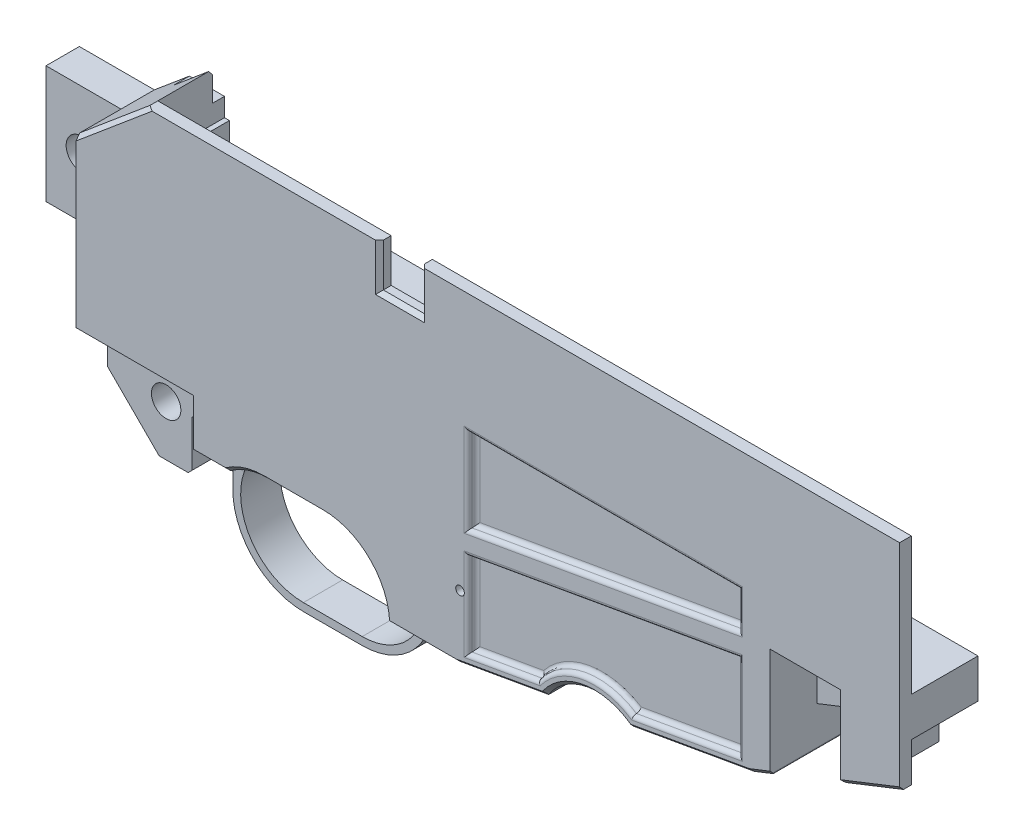
SolidWorks part; units mm, degrees
ref_plane "정면" through (0, 0, 0) normal (0, 0, 1) x (1, 0, 0)
ref_plane "윗면" through (0, 0, 0) normal (0, 1, 0) x (1, 0, 0)
ref_plane "우측면" through (0, 0, 0) normal (1, 0, 0) x (0, 0, -1)
sketch "스케치2" plane through (0, 0, 0) normal (0, 0, 1) x (1, 0, 0)
  line L0 (0, 0) -> (20, 0)
  line L1 (20, 0) -> (37.8763, 15)
  line L2 (37.8763, 15) -> (230, 15)
  line L3 (230, 15) -> (230, -54.9955)
  line L4 (230, -54.9955) -> (192, -54.9955)
  line L5 (117, -68.22) -> (101, -68.22)
  line L6 (0, 0) -> (0, -30)
  line L7 (0, -30) -> (20, -30)
  line L8 (20, -30) -> (20, -55)
  line L9 (20, -55) -> (33.22, -68.22)
  line L10 (33.22, -68.22) -> (50, -68.22)
  line L11 (117, -68.22) -> (139.5521, -64.2435)
  line L12 (68, -68.22) -> (83, -68.22) construction
  line L13 (68, -52.22) -> (83, -52.22)
  line L14 (68, -84.22) -> (83, -84.22)
  line L15 (161.2179, -60.4232) -> (192, -54.9955)
  line L16 (68, -86.22) -> (83, -86.22)
  line L17 (71.3269, -49.22) -> (86.3269, -49.22)
  line L19 (68, -50.22) -> (83, -50.22) construction
  arc A0 (68, -52.22) -> (68, -84.22) centre (68, -68.22) ccw
  arc A1 (83, -84.22) -> (83, -52.22) centre (83, -68.22) ccw
  arc A2 (83, -86.22) -> (101, -68.22) centre (83, -68.22) ccw
  arc A3 (50, -68.22) -> (68, -86.22) centre (68, -68.22) ccw
  arc A5 (139.5521, -64.2435) -> (161.2179, -60.4232) centre (152.1559, -72.3764) cw
  arc A6 (68, -50.22) -> (68, -86.22) centre (68, -68.22) ccw construction
  arc A7 (83, -86.22) -> (83, -50.22) centre (83, -68.22) ccw construction
  point P16 (75.5, -68.22)
  point P27 (50, -68.22)
  point P30 (101, -68.22)
  point P34 (139.5521, -64.2435)
  point P35 (161.2179, -60.4232)
  dimension "D11" = 16
  dimension "D15" = 22
  dimension "D16" = 15
  dimension "D1" = 230
  dimension "D2" = 30
  dimension "D3" = 30
  dimension "D4" = 135
  dimension "D5" = 140
  dimension "D6" = 15
  dimension "D7" = 75
  dimension "D8" = 16
  dimension "D9" = 15
  dimension "D12" = 3
  dimension "D13" = 64.22
  dimension "D14" = 170
  dimension "D17" = 20
  dimension "D18" = 25
  dimension "D19" = 16
  dimension "D20" = 22.9
  dimension "D21" = 20
  dimension "D10" = 2
extrude "보스-돌출1" add sketch "스케치2" along normal blind 20 contours A5 L15 L4 L3 L2 L1 L0 L6 L7 L8 L9 L10 A3 L16 A2 L5 A1 L14 A0 L13 region at (119.6066, -23.0148, 0)
sketch "스케치3" plane through (0, 0, 0) normal (0, 0, -1) x (-1, 0, 0)
  line L0 (-68, -52.22) -> (-83, -52.22) construction
  line L1 (-39.125, -49.22) -> (-111.875, -49.22)
  line L2 (-39.125, -49.22) -> (-39.125, 2.78)
  line L3 (-39.125, 2.78) -> (-111.875, 2.78)
  line L4 (-111.875, -49.22) -> (-111.875, 2.78)
  line L5 (-75.5, -52.22) -> (-75.5, -49.22) construction
  point P6 (-75.5, -52.22)
  point P9 (-75.5, -49.22)
  dimension "D1" = 52
  dimension "D2" = 72.75
  dimension "D3" = 3
extrude "컷-돌출1" cut sketch "스케치3" against normal blind 8.25
sketch "스케치4" plane through (0, 0, 0) normal (0, 0, -1) x (-1, 0, 0)
  line L1 (-37.8763, 2.78) -> (-211, 2.78)
  line L3 (-37.8763, 15) -> (-211, 15)
  line L4 (-211, 2.78) -> (-211, 15)
  line L5 (-37.8763, 2.78) -> (-37.8763, 15)
  line L6 (-211, -54.9955) -> (-211, 15) construction
  line L7 (-230, -54.9955) -> (-192, -54.9955) construction
  line L8 (-37.8763, 15) -> (-230, 15) construction
  dimension "D2" = 12.22
extrude "컷-돌출2" cut sketch "스케치4" against normal blind 17
sketch "스케치5" plane through (0, 0, 0) normal (0, 0, -1) x (-1, 0, 0)
  line L0 (-117, -68.22) -> (-117, 2.78)
  line L1 (-117, 2.78) -> (-192, 2.78)
  line L2 (-192, 2.78) -> (-192, -54.9955)
  line L3 (-211, 2.78) -> (-37.8763, 2.78) construction
  line L5 (-192, -54.9955) -> (-161.2179, -60.4232)
  line L6 (-139.5521, -64.2435) -> (-117, -68.22)
  line L7 (-117, -68.22) -> (-120.7282, -69.1071)
  arc A0 (-161.2179, -60.4232) -> (-139.5521, -64.2435) centre (-152.1559, -72.3764) cw
  line M11 (-192, -54.9955) -> (-161.2179, -60.4232)
  arc M12 (-161.2179, -60.4232) -> (-139.5521, -64.2435) centre (-152.1559, -72.3764) cw
  line M13 (-139.5521, -64.2435) -> (-117, -68.22)
extrude "컷-돌출3" cut sketch "스케치5" against normal blind 14 contours L1 L2 L0 M11 M12 M13 region at (153.265, -29.0527, 0)
sketch "스케치6" plane through (0, 0, 0) normal (0, 0, -1) x (-1, 0, 0)
  line L1 (-111.875, -49.22) -> (-39.125, -49.22) construction
  line L2 (-88, -49.22) -> (-63, -49.22)
  line L3 (-83, -52.22) -> (-68, -52.22)
  line L4 (-88, -49.22) -> (-88, -53.0213)
  line L6 (-63, -49.22) -> (-63, -53.0213)
  arc A2 (-68, -84.22) -> (-68, -52.22) centre (-68, -68.22) ccw construction
  arc A3 (-83, -52.22) -> (-83, -84.22) centre (-83, -68.22) ccw construction
  arc A4 (-63, -53.0213) -> (-68, -52.22) centre (-68, -68.22) ccw
  arc A5 (-83, -52.22) -> (-88, -53.0213) centre (-83, -68.22) ccw
  point P0 (-75.5, -49.22)
  dimension "D1" = 25
extrude "컷-돌출4" cut sketch "스케치6" against normal blind 5
sketch "스케치7" plane through (0, 0, 20) normal (0, 0, 1) x (1, 0, 0)
  line L0 (20, -42.5) -> (50, -42.5)
  line L1 (20, -30) -> (20, -55) construction
  line L2 (50, -42.5) -> (50, -68.22)
  line L3 (50, -68.22) -> (33.22, -68.22)
  line L4 (33.22, -68.22) -> (20, -55)
  line L5 (20, -55) -> (20, -42.5)
extrude "컷-돌출5" cut sketch "스케치7" against normal blind 8
sketch "스케치8" plane through (0, 0, 12) normal (0, 0, 1) x (1, 0, 0)
  line L0 (41.61, -68.22) -> (50, -68.22)
  line L1 (33.22, -68.22) -> (50, -68.22) construction
  line L2 (50, -68.22) -> (50, -55.36)
  line L3 (50, -68.22) -> (50, -42.5) construction
  line L4 (50, -55.36) -> (41.61, -55.36)
  line L5 (41.61, -55.36) -> (41.61, -68.22)
sketch "스케치9" plane through (0, -86.22, 0) normal (0, -1, 0) x (1, 0, 0)
  line L0 (75.5, 20) -> (50, 20)
  line L1 (68, 20) -> (83, 20) construction
  line L2 (50, 20) -> (50, 10)
  line L3 (50, 10) -> (101, 10)
  line L4 (101, 20) -> (101, 0) construction
  line L5 (101, 10) -> (101, 20)
  line L6 (101, 20) -> (75.5, 20)
  line L7 (75.5, 20) -> (75.5, 10)
  line M3 (83, 0) -> (83, 20)
  line M4 (83, 20) -> (68, 20)
  line M5 (68, 20) -> (68, 0)
  dimension "D1" = 10
extrude "컷-돌출7" cut sketch "스케치9" against normal up to surface (18 mm away) contours L5 L6 L3 M3 | L7 L3 M4 M3 region at (79.25, -86.22, 15) region at (92, -86.22, 15) up to face at (110.6, -68.22, 10.8)
extrude "컷-돌출9" cut sketch "스케치9<4>" against normal up to vertex (30.86 mm away) contours L7 L3 M4 M5 | L2 L3 L0 M5 region at (71.75, -86.22, 15) region at (59, -86.22, 15) up to point (50, -55.36, 12)
sketch "스케치9<4>" plane through (0, -86.22, 0) normal (0, -1, 0) x (1, 0, 0) same geometry as "스케치9"
fillet "필렛2" radius 7.5 1 edges at (54.2403, -55.36, 10) second distance 9 first distance on face at (72.5955, -74.4968, 10)
extrude "컷-돌출11" cut sketch "스케치8" against normal blind 6 contours L0 L2 L4 L5
chamfer "모따기2" distance 1 angle 45 1 edges at (41.61, -68.22, 9)
fillet "필렛3" radius 6 1 edges at (100, -68.22, 10) second distance 8 first distance on face at (107.2857, -68.22, 10.5714)
sketch "스케치11" plane through (0, 0, 0) normal (0, 0, -1) x (-1, 0, 0)
  line L1 (-230, 15) -> (-111.87, 15)
  line L2 (-230, 15) -> (-230, -20)
  line L3 (-230, -20) -> (-111.87, -20)
  line L4 (-111.87, 15) -> (-111.87, -20)
  dimension "D1" = 35
  dimension "D2" = 118.13
extrude "컷-돌출15" cut sketch "스케치11" against normal blind 17
sketch "스케치12" plane through (0, 0, 0) normal (0, 0, -1) x (-1, 0, 0)
  line L1 (-230, -54.9955) -> (-220, -54.9955)
  line L2 (-230, -54.9955) -> (-230, -29.9955)
  line L3 (-230, -29.9955) -> (-220, -29.9955)
  line L4 (-220, -54.9955) -> (-220, -29.9955)
  dimension "D1" = 10
  dimension "D2" = 25
extrude "컷-돌출16" cut sketch "스케치12" against normal blind 17
sketch "스케치16" plane through (0, 0, 20) normal (0, 0, 1) x (1, 0, 0)
  line L0 (192, -54.9955) -> (230, -39.9955)
  line L1 (230, 15) -> (230, -54.9955) construction
  line L2 (230, -39.9955) -> (230, -54.9955)
  line L3 (230, -54.9955) -> (192, -54.9955)
  dimension "D1" = 15
extrude "컷-돌출18" cut sketch "스케치16" against normal up to next
sketch "스케치17" plane through (0, 0, 20) normal (0, 0, 1) x (1, 0, 0)
  line L0 (37.8763, 15) -> (116.9763, 15) construction
  line L1 (37.8763, 15) -> (230, 15) construction
  line L2 (116.9763, 15) -> (116.9763, 13)
  line L3 (116.9763, 13) -> (190.9763, 13)
  line L4 (190.9763, 13) -> (190.9763, 15)
  line L5 (116.9763, 15) -> (190.9763, 15)
  dimension "D1" = 79.1
  dimension "D2" = 74
  dimension "D3" = 2
sketch "스케치20" plane through (0, 0, 0) normal (0, 0, -1) x (-1, 0, 0)
  line L1 (-117, -68.22) -> (-101, -68.22) construction
  line L2 (-117, -68.22) -> (-117, -20) construction
  line L3 (-113, -68.22) -> (-103, -68.22)
  line L4 (-103, -68.22) -> (-103, -50.22)
  line L5 (-103, -50.22) -> (-111.875, -50.22)
  line L6 (-111.875, -50.22) -> (-111.875, -36.22)
  line L8 (-111.875, -36.22) -> (-117, -36.22)
  line L9 (-117, -36.22) -> (-117, -64.22)
  line L10 (-117, -64.22) -> (-117, -68.22)
  line L11 (-117, -68.22) -> (-113, -68.22)
  dimension "D1" = 4
  dimension "D3" = 10
  dimension "D4" = 18
  dimension "D5" = 14
extrude "컷-돌출21" cut sketch "스케치20" against normal blind 6.25
fillet "필렛5" radius 2 1 edges at (103, -50.22, 3.125)
sketch "스케치22" plane through (0, 0, 12) normal (0, 0, 1) x (1, 0, 0)
  line L0 (20, -42.5) -> (50, -68.22) construction
  circle A0 centre (35, -55.36) radius 3.75
  dimension "D1" = 7.5
extrude "컷-돌출23" cut sketch "스케치22" against normal up to next
chamfer "모따기3" distance 1 angle 45 1 edges at (111.875, -50.22, 3.125)
sketch "스케치23" plane through (117, 0, 0) normal (1, 0, 0) x (0, 0, -1)
  line L0 (-6.5, -33.22) -> (-6.5, -68.22)
  line L3 (0, -36.22) -> (0, -20) construction
  line L4 (-6.5, -33.22) -> (0, -33.22)
  line L5 (0, -33.22) -> (0, -68.22)
  line L6 (0, -68.22) -> (-6.5, -68.22)
  dimension "D1" = 6.5
  dimension "D2" = 35
  dimension "D3" = 6.5
sketch "스케치25" plane through (0, 0, 20) normal (0, 0, 1) x (1, 0, 0)
  line L1 (0, 0) -> (20, 0)
  line L2 (0, 0) -> (0, -30)
  line L3 (0, -30) -> (20, -30)
  line L4 (20, 0) -> (20, -30)
extrude "컷-돌출26" cut sketch "스케치25" against normal blind 11.5
sketch "스케치30" plane through (0, 0, 20) normal (0, 0, 1) x (1, 0, 0)
  line L0 (117, -68.22) -> (117, 0)
  line L1 (117, 0) -> (192, 0)
  line L2 (192, 0) -> (192, -54.9955)
  line L3 (117, -68.22) -> (139.5521, -64.2435) construction
  line L4 (161.2179, -60.4232) -> (192, -54.9955) construction
  line L5 (117, -68.22) -> (139.5521, -64.2435)
  line L6 (161.2179, -60.4232) -> (192, -54.9955)
  line L7 (120, -64.6447) -> (137.8102, -61.5043)
  line L8 (120, -64.6447) -> (120, -15.7418)
  line L9 (120, -3) -> (174.9862, -3)
  line L10 (189, -3.5753) -> (189, -52.4782)
  line L11 (161.9179, -57.2535) -> (189, -52.4782)
  line L12 (117, -13.2245) -> (192, 0)
  line L13 (120, -15.7418) -> (189, -3.5753)
  line L14 (120, -12.6955) -> (120, -3)
  line L15 (120, -3) -> (189, -3) construction
  line L16 (102.969, -15.6986) -> (201.3298, 1.6451) construction
  line L17 (103.49, -18.653) -> (201.8507, -1.3093) construction
  line L18 (189, -3) -> (189, -52.4782) construction
  line L19 (189, -28.0267) -> (120, -40.1933)
  line L20 (120, -64.6447) -> (120, -3) construction
  line L21 (189, -25.0723) -> (120, -37.2389)
  line L22 (189, -30.9811) -> (120, -43.1477)
  line L23 (120, -15.7418) -> (189, -15.7418)
  arc A0 (161.2179, -60.4232) -> (139.5521, -64.2435) centre (152.1559, -72.3764) ccw construction
  arc A1 (161.2179, -60.4232) -> (139.5521, -64.2435) centre (152.1559, -72.3764) ccw
  arc A2 (161.9179, -57.2535) -> (137.8102, -61.5043) centre (152.1559, -72.3764) ccw
  dimension "D2" = 3
  dimension "D1" = 3
extrude "컷-돌출27" cut sketch "스케치30" against normal blind 2 contours A2 L11 L10 L9 L8 L7 | L23 L8 L21 L10 region at (154.7863, -47.2575, 20) region at (149.9613, -23.8488, 20)
fillet "필렛6" radius 1 20 edges at (128.9051, -63.0745, 20) (128.9051, -63.0745, 18) (149.0302, -54.6499, 20) (149.0302, -54.6499, 18) (175.4589, -54.8658, 18) (175.4589, -54.8658, 20) (189, -41.7297, 20) (120, -53.8962, 20) (120, -53.8962, 18) (189, -41.7297, 18) (154.5, -37.0644, 20) (154.5, -37.0644, 18) (189, -20.4071, 20) (189, -20.4071, 18) (154.5, -31.1556, 20) (154.5, -31.1556, 18) (120, -26.4903, 18) (120, -26.4903, 20) (154.5, -15.7418, 18) (154.5, -15.7418, 20)
sketch "스케치32" plane through (37.8763, 0, 0) normal (1, 0, 0) x (0, 0, -1)
  line L1 (0, 15) -> (-3, 15)
  line L2 (0, 15) -> (0, 7.5)
  line L3 (0, 7.5) -> (-3, 7.5)
  line L4 (-3, 15) -> (-3, 7.5)
  dimension "D1" = 3
  dimension "D2" = 7.5
extrude "컷-돌출28" cut sketch "스케치32" against normal blind 10
chamfer "모따기5" distance 1 angle 45 1 edges at (33.4072, 11.25, 3)
sketch "스케치33" plane through (0, -68.22, 0) normal (0, -1, 0) x (1, 0, 0)
  line L0 (33.22, 0) -> (50, 0) construction
  circle A0 centre (43.375, 0) radius 2
  dimension "D2" = 4
  dimension "D1" = 6.625
extrude "컷-돌출29" cut sketch "스케치33" against normal through all
chamfer "모따기6" distance 1 angle 45 1 edges at (43.375, -68.22, 2)
sketch "스케치34" plane through (0, -49.22, 0) normal (0, 1, 0) x (1, 0, 0)
  line L0 (111.875, 0) -> (88, 0) construction
  line L1 (101.6, 0) -> (97.65, 0)
  circle A0 centre (99.625, 0) radius 1.975
  line M8 (111.875, 0) -> (88, 0)
  dimension "D2" = 3.95
  dimension "D1" = 12.25
extrude "보스-돌출2" add sketch "스케치34" along normal blind 2 contours A0 M8 region at (99.625, -49.22, 0.8382)
chamfer "모따기7" distance 0.5 angle 45 1 edges at (99.625, -47.22, 1.975)
sketch "스케치35" plane through (0, 0, 8.5) normal (0, 0, 1) x (1, 0, 0)
  line L0 (0, 0) -> (20, -30) construction
  circle A0 centre (10, -15) radius 4
  dimension "D1" = 8
extrude "컷-돌출30" cut sketch "스케치35" against normal through all
chamfer "모따기8" distance 1 angle 45 10 edges at (54.2403, -55.36, 20) (28.9382, 7.5, 20) (62.988, -53.0253, 20) (94.3137, -56.9063, 20) (75.5, -52.22, 20) (211, -47.4955, 20) (176.6089, -57.7093, 20) (149.5511, -57.6043, 20) (128.276, -66.2317, 20) (108, -68.22, 20)
sketch "스케치36" plane through (0, 0, 8.25) normal (0, 0, -1) x (-1, 0, 0)
  line L0 (-111.875, -49.22) -> (-39.125, -49.22) construction
  line L1 (-51.125, -43.22) -> (-93.125, -43.22)
  line L2 (-51.125, -43.22) -> (-51.125, -3.22)
  line L3 (-51.125, -3.22) -> (-93.125, -3.22)
  line L4 (-93.125, -43.22) -> (-93.125, -3.22)
  line L5 (-39.125, -49.22) -> (-39.125, 2.78) construction
  line L6 (-57.125, -3.22) -> (-93.125, -39.22)
  line L7 (-51.125, -8.22) -> (-86.125, -43.22)
  dimension "D1" = 6
  dimension "D2" = 12
  dimension "D3" = 42
  dimension "D4" = 40
  dimension "D5" = 45
  dimension "D6" = 45
  dimension "D7" = 4
  dimension "D8" = 35
extrude "컷-돌출31" cut sketch "스케치36" against normal blind 8 contours L6 L3 L4 | L2 L7 L1 region at (62.7917, -31.5533, 8.25) region at (81.125, -15.22, 8.25)
sketch "스케치37" plane through (0, 0, 8.25) normal (0, 0, -1) x (-1, 0, 0)
  line L0 (-111.87, -20) -> (-111.87, 2.78) construction
  line L1 (-111.875, -49.22) -> (-39.125, -49.22) construction
  line L2 (-39.125, -49.22) -> (-39.125, 2.78) construction
  line L3 (-111.875, -20) -> (-111.875, -49.22) construction
  circle A0 centre (-106.817, -8.72) radius 2.5
  circle A1 centre (-44.625, -24.22) radius 2.5
  circle A2 centre (-99.637, -35.72) radius 2.5
  dimension "D1" = 5
  dimension "D4" = 5
  dimension "D9" = 5
  dimension "D2" = 5.053
  dimension "D3" = 40.5
  dimension "D5" = 5.5
  dimension "D6" = 25
  dimension "D7" = 12.238
  dimension "D8" = 13.5
extrude "컷-돌출32" cut sketch "스케치37" against normal blind 4
fillet "필렛7" radius 0.5 3 edges at (42.125, -24.22, 8.25) (104.317, -8.72, 8.25) (97.137, -35.72, 8.25)
chamfer "모따기9" distance 2 angle 47 1 edges at (63, -53.0213, 2.5) first distance on face at (63, -51.1207, 2.5)
sketch "스케치38" plane through (0, 0, 20) normal (0, 0, 1) x (1, 0, 0)
  line L0 (192, -20) -> (192, -54.9955) construction
  line L1 (197, -25) -> (215, -25)
  line L2 (197, -25) -> (197, -61.0759)
  line L3 (197, -61.0759) -> (215, -61.0759)
  line L4 (215, -25) -> (215, -61.0759)
  line L5 (230, -20) -> (111.87, -20) construction
  dimension "D1" = 18
  dimension "D2" = 5
  dimension "D3" = 5
extrude "컷-돌출33" cut sketch "스케치38" against normal blind 12
sketch "스케치41" plane through (0, 0, 8) normal (0, 0, 1) x (1, 0, 0)
  line L0 (215, -35.9165) -> (197, -43.0218)
  line L1 (215, -45.9165) -> (215, -25) construction
  line L2 (197, -25) -> (197, -53.0218) construction
  line L3 (197, -53.0218) -> (215, -45.9165) construction
  line L4 (197, -43.0218) -> (197, -53.0218)
  line L5 (197, -53.0218) -> (215, -45.9165)
  line L6 (215, -45.9165) -> (215, -35.9165)
  dimension "D1" = 10
extrude "컷-돌출37" cut sketch "스케치41" against normal up to next
fillet "필렛9" radius 0.5 2 edges at (215, -45.9165, 9.5) (197, -53.0218, 9.5)
sketch "스케치43" plane through (0, 0, 8) normal (0, 0, 1) x (1, 0, 0)
  line L0 (215, -27.9165) -> (197, -35.0218) construction
  line L2 (197, -25) -> (197, -43.0218) construction
  line L3 (215, -35.9165) -> (197, -43.0218) construction
  circle A0 centre (206, -31.4692) radius 4
  dimension "D1" = 8
  dimension "D2" = 8
extrude "컷-돌출38" cut sketch "스케치43" against normal up to next
fillet "필렛10" radius 1 1 edges at (210, -31.4692, 8)
sketch "스케치44" plane through (0, 0, 20) normal (0, 0, 1) x (1, 0, 0)
  line L0 (39.432, 15) -> (97.382, 15) construction
  line L1 (39.432, 15) -> (230, 15) construction
  line L2 (97.382, 15) -> (97.382, 4)
  line L3 (97.382, 4) -> (107.882, 4)
  line L4 (107.882, 4) -> (107.882, 15)
  line L5 (97.382, 15) -> (107.882, 15)
  dimension "D1" = 57.95
  dimension "D2" = 10.5
  dimension "D3" = 11
extrude "컷-돌출39" cut sketch "스케치44" against normal up to surface (3 mm away) up to face at (126.5821, -0.74, 17)
sketch "스케치45" plane through (0, 0, 14) normal (0, 0, -1) x (-1, 0, 0)
  line L0 (-117, -20) -> (-125, -20)
  line L1 (-192, -20) -> (-117, -20) construction
  line L2 (-125, -20) -> (-125, -66.8094)
  line L3 (-139.5521, -64.2435) -> (-117, -68.22) construction
  line L4 (-125, -66.8094) -> (-117, -68.22)
  line L5 (-117, -68.22) -> (-117, -20)
  dimension "D1" = 8
extrude "보스-돌출3" add sketch "스케치45" along normal up to surface (7.75 mm away) up to face at (109.9013, -51.2932, 6.25)
sketch "스케치46" plane through (125, 0, 0) normal (1, 0, 0) x (0, 0, -1)
  line L2 (0, -68.22) -> (-6.5, -68.22) construction
  line L3 (0, -20) -> (0, -68.22)
  line L4 (-6.5, -20) -> (-6.5, -68.22)
  line L5 (0, -68.22) -> (-6.5, -68.22)
  line L7 (-6.25, -20) -> (-14, -20) construction
  line L8 (-6.5, -20) -> (0, -20)
extrude "컷-돌출40" cut sketch "스케치46" against normal blind 2
sketch "스케치47" plane through (0, 0, 6.25) normal (0, 0, -1) x (-1, 0, 0)
  line L0 (-123, -67.162) -> (-111.875, -36.22) construction
  circle A0 centre (-117.4375, -51.691) radius 2.5
  dimension "D1" = 5
extrude "컷-돌출41" cut sketch "스케치47" against normal blind 3
sketch "스케치48" plane through (0, 0, 9.25) normal (0, 0, -1) x (-1, 0, 0)
  circle A0 centre (-117.9375, -51.6029) radius 1.1
  dimension "D1" = 2.2
extrude "컷-돌출42" cut sketch "스케치48" against normal through all
sketch "스케치50" plane through (0, 0, 6.25) normal (0, 0, -1) x (-1, 0, 0)
  line L0 (-123, -67.162) -> (-117, -68.22)
  line L1 (-117, -68.22) -> (-115.95, -68.22)
  line L2 (-117, -68.22) -> (-103, -68.22) construction
  line L3 (-123, -67.162) -> (-123, -20) construction
  line L4 (-123, -56.362) -> (-123, -67.162)
  line L5 (-115.95, -68.22) -> (-116.4479, -61.1)
  line L6 (-116.4479, -61.1) -> (-123, -56.362)
  dimension "D1" = 10.8
  dimension "D2" = 1.05
  dimension "D3" = 86
  dimension "D4" = 7.12
extrude "보스-돌출4" add sketch "스케치50" along normal up to surface (6.25 mm away) up to face at (14, -15, 0)
sketch "스케치51" plane through (120.133, -8.4005, 0) normal (-0.9976, 0.0698, 0) x (0, 0, 1)
  line L0 (0, -52.8282) -> (0, -59.9656) construction
  circle A0 centre (0, -55.3282) radius 2
  dimension "D1" = 4
  dimension "D2" = 2.5
extrude "컷-돌출43" cut sketch "스케치51" against normal blind 4.5
chamfer "모따기10" distance 1 angle 45 1 edges at (102.632, 4, 20)
chamfer "모따기11" distance 1 angle 45 2 edges at (107.882, 9, 20) (97.382, 9, 20)
chamfer "모따기12" distance 1 angle 41 3 edges at (0, -30, 4.25) (0, 0, 4.25) (0, -15, 8.5) first distance on face at (0, -15, 4.25)
